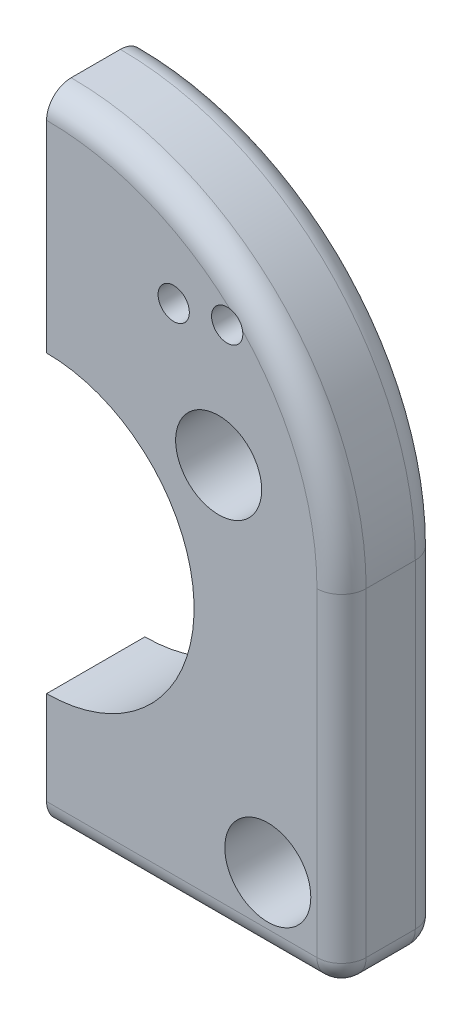
SolidWorks part; units mm, degrees
ref_plane "Front Plane" through (0, 0, 0) normal (0, 0, 1) x (1, 0, 0)
ref_plane "Top Plane" through (0, 0, 0) normal (0, 1, 0) x (1, 0, 0)
ref_plane "Right Plane" through (0, 0, 0) normal (1, 0, 0) x (0, 0, -1)
sketch "Sketch1" plane through (0, 0, 0) normal (0, 0, 1) x (1, 0, 0)
  line L0 (0, 0) -> (0, 95.25) construction
  line L1 (-19.05, 0) -> (19.05, 0)
  line L2 (-19.05, 0) -> (-19.05, 15.24)
  line L3 (-19.05, 82.55) -> (22.5557, 82.55) construction
  line L4 (19.05, 0) -> (19.05, 44.45)
  line L5 (-19.05, 53.34) -> (-19.05, 82.55)
  circle A0 centre (9.525, 9.525) radius 5.5563
  circle A1 centre (3.175, 51.9145) radius 5.5562
  arc A2 (-19.05, 82.55) -> (19.05, 44.45) centre (-19.05, 44.45) cw
  arc A3 (-19.05, 15.24) -> (-19.05, 53.34) centre (-19.05, 34.29) ccw
  dimension "D3" = 11.1125
  dimension "D4" = 11.1125
  dimension "D9" = 38.1
  dimension "D10" = 34.29
  dimension "D1" = 38.1
  dimension "D2" = 82.55
  dimension "D5" = 9.525
  dimension "D6" = 3.175
  dimension "D7" = 42.8625
  dimension "D8" = 9.525
extrude "Boss-Extrude1" add sketch "Sketch1" along normal blind 12.7
hole_wizard "#10-32 Tapped Hole2" positions "Sketch5" profile "Sketch6" tap size "#10-32" standard "ANSI Inch" end condition through all
sketch "Sketch5" plane through (0, 0, 12.7) normal (0, 0, 1) x (1, 0, 0)
  line L2 (-2.6308, 67.0969) -> (4.2771, 68.1317) construction
  line L3 (3.175, 51.9145) -> (9.525, 9.525) construction
  line L5 (3.175, 51.9145) -> (-5.7345, 111.3902) construction
  point P0 (-2.6308, 67.0969)
  point P2 (4.2771, 68.1317)
  dimension "D1" = 6.985
  dimension "D2" = 3.4925
  dimension "D3" = 58.7375
sketch "Sketch6" plane through (-2.6308, 67.0969, 12.7) normal (1, 0, 0) x (0, -1, 0)
  line L0 (0, 0) -> (0, 12.7)
  line L1 (0, 12.7) -> (2.0193, 12.7)
  line L2 (2.0193, 12.7) -> (2.0193, 0)
  line L5 (2.0193, 0) -> (0, 0)
  line L11 (0, -6.35) -> (0, 107.95) construction
  dimension "Thru Tap Drill Dia." = 4.0386
  dimension "Thru Tap Drill Depth" = 12.7
cosmetic thread "Hole Thread3" parameters "D2"=4.826
cosmetic thread "Hole Thread4" parameters "D2"=4.826
hole_wizard "#10-32 Tapped Hole3" positions "Sketch8" profile "Sketch9" tap size "#10-32" standard "ANSI Inch"
sketch "Sketch8" plane through (-19.05, 0, 0) normal (-1, 0, 0) x (0, 0, 1)
  line L4 (12.7, 53.34) -> (0, 53.34) construction
  line L5 (6.35, 0) -> (6.35, 15.24) construction
  line L6 (12.7, 0) -> (0, 0) construction
  line L7 (12.7, 15.24) -> (0, 15.24) construction
  point P0 (6.35, 7.62)
  point P2 (6.35, 60.96)
  dimension "D3" = 7.62
  dimension "D4" = 53.34
sketch "Sketch9" plane through (-19.05, 7.62, 6.35) normal (0, 1, 0) x (0, 0, 1)
  line L0 (0, 0) -> (0, 17.2153)
  line L1 (0, 17.2153) -> (2.0193, 16.002)
  line L2 (2.0193, 16.002) -> (2.0193, 0)
  line L5 (2.0193, 0) -> (0, 0)
  line L10 (0, 17.2153) -> (-2.0193, 16.002) construction
  line L11 (0, -6.35) -> (0, 107.95) construction
  dimension "Tap Drill Dia." = 4.0386
  dimension "Tap Drill Depth" = 16.002
  dimension "Drill Angle" = 118
cosmetic thread "Hole Thread5" parameters "D1"=10.16, "D2"=4.826
cosmetic thread "Hole Thread6" parameters "D1"=10.16, "D2"=4.826
fillet "Fillet1" radius 3.175 7 edges at (19.05, 22.225, 12.7) (7.8908, 71.3908, 0) (0, 0, 12.7) (19.05, 0, 6.35) (7.8908, 71.3908, 12.7) (19.05, 22.225, 0) (0, 0, 0)
equation "\"D2@Sketch5\"=\"D1@Sketch5\"/2"
